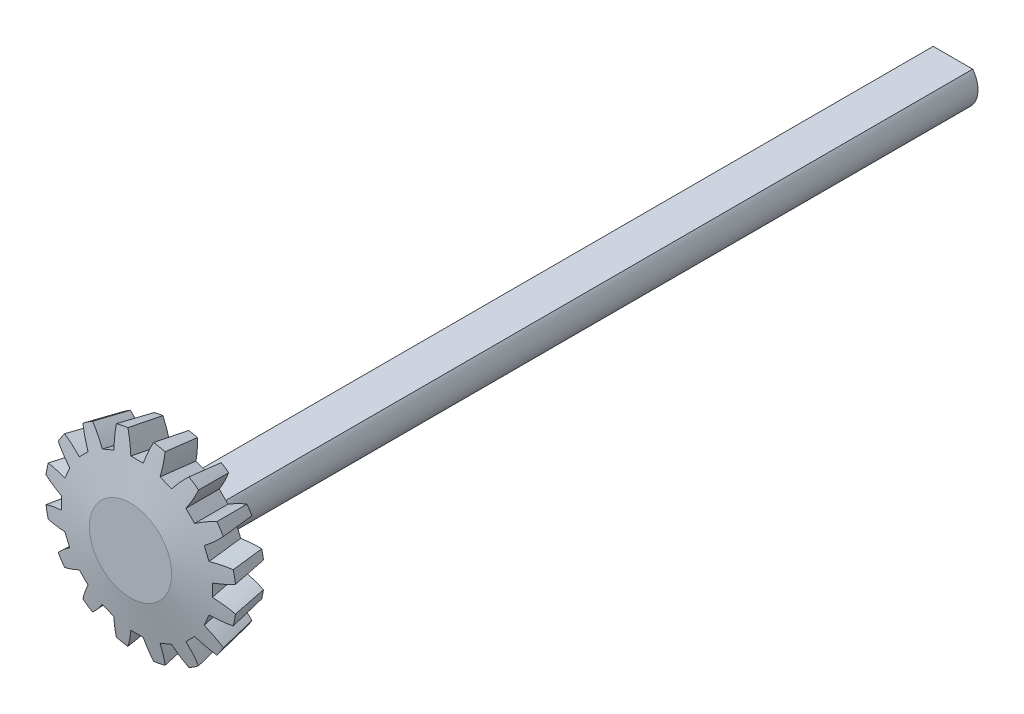
SolidWorks part; units mm, degrees
ref_plane "Front Plane" through (0, 0, 0) normal (0, 0, 1) x (1, 0, 0)
ref_plane "Top Plane" through (0, 0, 0) normal (0, 1, 0) x (1, 0, 0)
ref_plane "Right Plane" through (0, 0, 0) normal (1, 0, 0) x (0, 0, -1)
sketch "Sketch2" plane through (0, 0, 0) normal (1, 0, 0) x (0, 0, -1)
  line L0 (0, 0) -> (0, 4)
  line L1 (1, 9.3) -> (4.4126, 8.6175)
  line L2 (4.4126, 8.6175) -> (4.4126, 0)
  line L3 (4.4126, 0) -> (0, 0)
  line L4 (0, 4) -> (1, 9.3)
  line L5 (0, 4) -> (0, 9.5) construction
  line L6 (1, 9.3) -> (0, 9.5) construction
  dimension "D1" = 78.69
  dimension "D2" = 1
  dimension "D3" = 9.5
  dimension "D4" = 4
  dimension "D5" = 4.5
revolve "Revolve1" add sketch "Sketch2" angle 360 about L3
ref_axis "Axis1" through (0, 0, -1) along (0, 0, -1)
sketch "Sketch4" plane through (0, 0, 0) normal (1, 0, 0) x (0, 0, -1)
  line L0 (1, 9.3) -> (4.4126, 8.6175) construction
ref_plane "Plane1" through (0, 8.6175, -4.4126) normal (0, -0.1961, -0.9806) x (-1, 0, 0)
ref_plane "Plane2" through (0, 8.4214, -5.3932) normal (0, -0.1961, -0.9806) x (-1, 0, 0)
sketch "Sketch6" plane through (0, 8.4214, -5.3932) normal (0, -0.1961, -0.9806) x (-1, 0, 0)
  line L0 (0, 0) -> (0, -2) construction
  line L1 (-0.6, -2) -> (0.6, -2)
  arc A0 (-1.75, 0.8873) -> (-0.6, -2) centre (-11.045, -4.4875) cw
  arc A1 (1.75, 0.8873) -> (0.6, -2) centre (11.045, -4.4875) ccw
  arc A2 (1.75, 0.8873) -> (-1.75, 0.8873) centre (0, -8.4501) ccw
  ellipse E0 centre (0, -8.4501) end of major axis (8.6175, -8.4501) minor radius 8.4501 construction
  ellipse E1 centre (0, -8.4501) end of major axis (8.6175, -8.4501) minor radius 8.4501 (1.25, -0.0894) -> (-1.25, -0.0894) ccw construction
  point P10 (-1.25, -0.0894)
  dimension "D5" = 19
  dimension "D1" = 2
  dimension "D2" = 1.25
  dimension "D3" = 3.5
  dimension "D4" = 0.6
extrude "Cut-Extrude1" cut sketch "Sketch6" against normal through all contours A0 L1 A1 A2
pattern_circular "CirPattern1" count 16 over 360 about axis through (0, 0, -1) along (0, 0, -1) of "Cut-Extrude1"
sketch "Sketch7" plane through (0, 0, -4.4126) normal (0, 0, -1) x (-1, 0, 0)
  line L0 (-1.92, 1.5) -> (1.92, 1.5)
  arc A0 (-1.92, 1.5) -> (1.92, 1.5) centre (0, 0) ccw
  dimension "D1" = 4.873
  dimension "D2" = 1.5
extrude "Boss-Extrude2" add sketch "Sketch7" along normal blind 80 from surface starting at face at (0, 4, 0)
